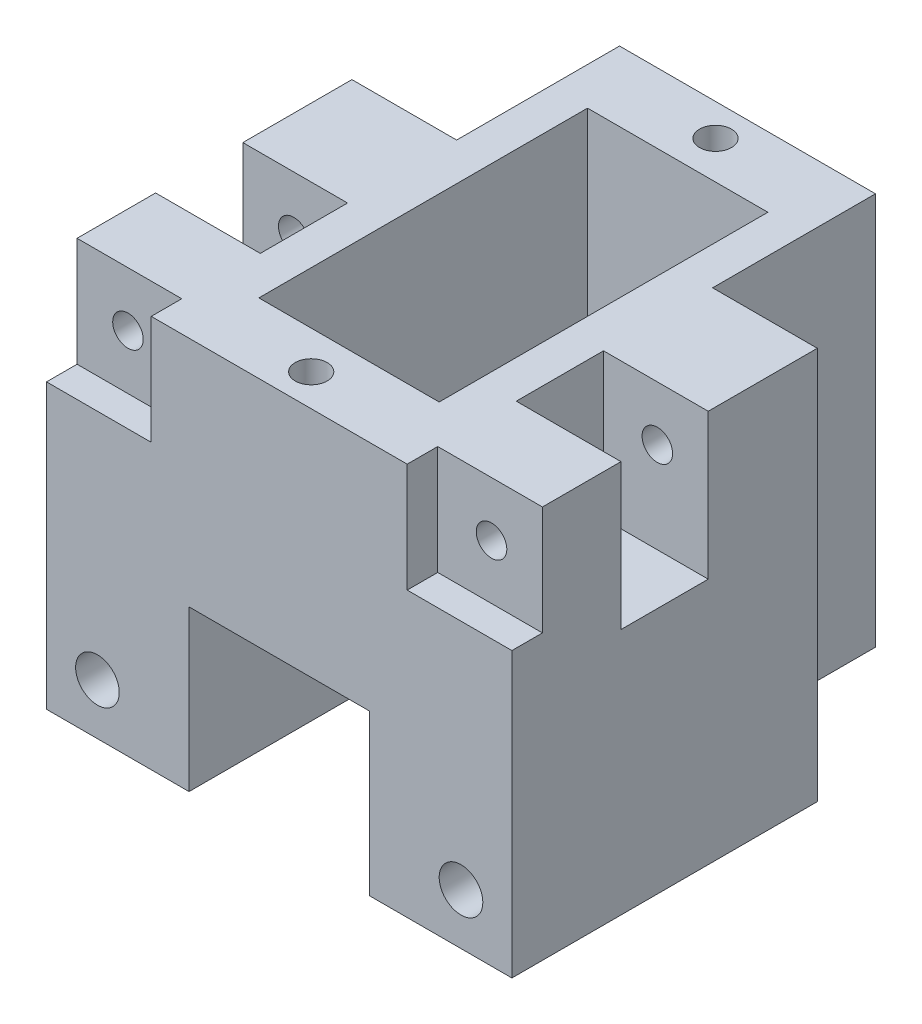
SolidWorks part; units mm, degrees
ref_plane "Front Plane" through (0, 0, 0) normal (0, 0, 1) x (1, 0, 0)
ref_plane "Top Plane" through (0, 0, 0) normal (0, 1, 0) x (1, 0, 0)
ref_plane "Right Plane" through (0, 0, 0) normal (1, 0, 0) x (0, 0, -1)
sketch "Sketch1" plane through (0, 0, 0) normal (0, 1, 0) x (1, 0, 0)
  line L0 (0, 0) -> (200, 0)
  line L1 (200, 0) -> (200, 47.5)
  line L2 (200, 47.5) -> (145, 47.5)
  line L3 (145, 47.5) -> (145, 117.5)
  line L4 (145, 117.5) -> (200, 117.5)
  line L5 (200, 117.5) -> (200, 144.5)
  line L7 (0, 144.5) -> (0, 117.5)
  line L8 (0, 117.5) -> (55, 117.5)
  line L9 (55, 117.5) -> (55, 47.5)
  line L10 (55, 47.5) -> (0, 47.5)
  line L11 (0, 47.5) -> (0, 0)
  line L12 (100, 0) -> (100, 178.8662) construction
  line L13 (84, 77) -> (116, 77)
  line L14 (84, 77) -> (84, 98)
  line L15 (84, 98) -> (91.2, 98)
  line L16 (116, 98) -> (116, 77)
  line L17 (93.8, 98) -> (93.8, 77)
  line L18 (106.2, 98) -> (106.2, 77)
  line L19 (93.8, 81.8) -> (106.2, 81.8)
  line L20 (93.8, 98) -> (93.8, 104.4)
  line L21 (93.8, 104.4) -> (106.2, 104.4)
  line L22 (106.2, 104.4) -> (106.2, 98)
  line L23 (108.8, 98) -> (116, 98)
  line L24 (91.2, 98) -> (91.2, 109.2)
  line L25 (91.2, 109.2) -> (108.8, 109.2)
  line L26 (108.8, 109.2) -> (108.8, 98)
  line L27 (80, 0) -> (80, -20)
  line L28 (80, -20) -> (90, -20)
  line L29 (90, -20) -> (90, 0)
  line L30 (120, -20) -> (110, -20)
  line L31 (110, -20) -> (110, 0)
  line L32 (120, 0) -> (120, -20)
  line L33 (20, 144.5) -> (180, 144.5) construction
  line L34 (145, 117.5) -> (200, 144.5)
  line L35 (0, 144.5) -> (55, 117.5)
  arc A0 (0, 144.5) -> (200, 144.5) centre (100, 16.1913) cw
  arc A1 (20, 144.5) -> (180, 144.5) centre (100, 29.6087) cw construction
  circle A2 centre (91, 93) radius 1.5
  circle A3 centre (91, 82) radius 1.5
  circle A4 centre (109, 82) radius 1.5
  circle A5 centre (109, 93) radius 1.5
  point P12 (100, 0)
  point P14 (100, 77)
  point P21 (100, 85.5)
  point P34 (80, 0)
  point P43 (55, 82.5)
  point P48 (100, 144.5)
  dimension "D23" = 162.6749
  dimension "D26" = 140
  dimension "D28" = 3
  dimension "D29" = 3
  dimension "D30" = 3
  dimension "D31" = 3
  dimension "D32" = 5
  dimension "D33" = 5
  dimension "D3" = 35
  dimension "D4" = 200
  dimension "D5" = 45
  dimension "D6" = 45
  dimension "D7" = 77
  dimension "D8" = 32
  dimension "D9" = 21
  dimension "D10" = 16
  dimension "D11" = 12.4
  dimension "D12" = 6.2
  dimension "D13" = 4.8
  dimension "D14" = 22.6
  dimension "D15" = 4.8
  dimension "D16" = 7.2
  dimension "D17" = 7.2
  dimension "D18" = 20
  dimension "D19" = 10
  dimension "D20" = 20
  dimension "D21" = 5.5
  dimension "D22" = 70
  dimension "D24" = 27
  dimension "D25" = 27
  dimension "D27" = 160
  dimension "D34" = 7
  dimension "D36" = 7
extrude "Boss-Extrude2" add sketch "Sketch1" along normal blind 27 from offset 2 contours L26 L25 L24 L15 L14 L13 L17 L20 L21 L22 L18 L16 L23 | L19 L17 L13 L18 | A3 | A2 | A5 | A4 region at (84.454, 0, -87.5) region at (100, 0, -79.4) region at (91, 0, -93) region at (91, 0, -82) region at (109, 0, -82) region at (109, 0, -93)
ref_plane "Plane1" through (0, 29, 0) normal (0, 1, 0) x (1, 0, 0)
sketch "Sketch2" plane through (0, 29, 0) normal (0, 1, 0) x (1, 0, 0)
  line L0 (84, 78.9953) -> (84, 84.5)
  line L1 (84, 84.5) -> (84, 77)
  line L2 (116, 80.7116) -> (116, 85.2116)
  line L3 (116, 85.2116) -> (116, 77)
  line L4 (116, 79.1) -> (108.8, 79.1)
  line L5 (108.8, 79.1) -> (108.8, 77)
  line L6 (91.2, 77) -> (91.2, 79.1)
  line L7 (91.2, 79.1) -> (84, 79.1)
  line L8 (91.2, 98) -> (84, 98)
  line L11 (91.2, 98) -> (84, 98)
  line L13 (84, 98) -> (84, 77)
  line L24 (116, 84.5) -> (108.8, 84.5)
  line L25 (108.8, 84.5) -> (108.8, 90.5)
  line L26 (108.8, 90.5) -> (116, 90.5)
  line L27 (100, 0) -> (100, 178.8662) construction
  line L28 (100, 0) -> (100, 178.8662) construction
  line L29 (84, 84.5) -> (91.2, 84.5)
  line L30 (91.2, 84.5) -> (91.2, 90.5)
  line L31 (91.2, 90.5) -> (84, 90.5)
  line L32 (84, 98) -> (84, 77)
  line L44 (84, 77) -> (116, 77)
  line L45 (84, 77) -> (116, 77)
  line L47 (116, 77) -> (116, 98)
  line L49 (116, 77) -> (116, 98)
  line L51 (116, 98) -> (108.8, 98)
  line L53 (116, 98) -> (108.8, 98)
  line L55 (108.8, 98) -> (108.8, 109.2)
  line L56 (108.8, 98) -> (108.8, 109.2)
  line L57 (108.8, 109.2) -> (91.2, 109.2)
  line L58 (108.8, 109.2) -> (91.2, 109.2)
  line L59 (91.2, 109.2) -> (91.2, 98)
  line L60 (91.2, 109.2) -> (91.2, 98)
  point P21 (116, 87.5)
  dimension "D4" = 7.2
  dimension "D5" = 7.2
  dimension "D6" = 6
  dimension "D7" = 3
  dimension "D1" = 0
extrude "Cut-Extrude1" cut sketch "Sketch2" against normal blind 7.5 contours L5 L45 L3 L4 | L1 L45 L6 L7 L0 region at (87.6, 29, -78.05) region at (112.4, 29, -78.05)
ref_plane "Plane2" through (0, 0, -77) normal (0, 0, 1) x (1, 0, 0)
sketch "Sketch3" plane through (0, 0, -77) normal (0, 0, 1) x (1, 0, 0)
  line L0 (93.8, 29) -> (106.2, 29) construction
  line L1 (93.8, 29) -> (106.2, 29)
  line L2 (93.8, 29) -> (93.8, 2) construction
  line L4 (106.2, 29) -> (106.2, 2) construction
  line L5 (93.8, 13) -> (106.2, 13)
  line L6 (93.8, 13) -> (93.8, 2)
  line L7 (106.2, 13) -> (106.2, 2)
  line L8 (84, 2) -> (116, 2) construction
  line L9 (93.8, 29) -> (93.8, 2) construction
  line L10 (106.2, 29) -> (106.2, 2) construction
  line L11 (84, 2) -> (116, 2)
  dimension "D1" = 16
extrude "Cut-Extrude2" cut sketch "Sketch3" against normal through all both and the other way through all contours L6 L7 L5 region at (100, 7.5, -77)
extrude "Cut-Extrude3" cut sketch "Sketch2<3>" against normal blind 10 contours L26 L25 L24 L49 | L30 L31 L32 L29 region at (87.6, 29, -87.5) region at (112.4, 29, -87.5)
sketch "Sketch2<3>" plane through (0, 29, 0) normal (0, 1, 0) x (1, 0, 0) same geometry as "Sketch2"
sketch "Sketch7" plane through (0, 0, -77) normal (0, 0, 1) x (1, 0, 0)
  line L0 (116, 29) -> (108.8, 29) construction
  line L1 (108.8, 29) -> (108.8, 21.5) construction
  line L2 (108.8, 21.5) -> (116, 21.5) construction
  line L3 (116, 21.5) -> (116, 29) construction
  line L4 (91.2, 29) -> (84, 29) construction
  line L5 (84, 29) -> (84, 21.5) construction
  line L6 (84, 21.5) -> (91.2, 21.5) construction
  line L7 (91.2, 21.5) -> (91.2, 29) construction
  line L8 (116, 29) -> (108.8, 29) construction
  line L9 (108.8, 29) -> (108.8, 21.5) construction
  line L10 (108.8, 21.5) -> (116, 21.5) construction
  line L11 (116, 21.5) -> (116, 29) construction
  line L12 (91.2, 29) -> (84, 29) construction
  line L13 (84, 29) -> (84, 21.5)
  line L14 (84, 21.5) -> (91.2, 21.5) construction
  line L15 (91.2, 21.5) -> (91.2, 29) construction
  line L16 (106.2, 2) -> (116, 2) construction
  line L21 (84, 21.5) -> (84, 2) construction
  line L22 (116, 21.5) -> (116, 2) construction
  line L24 (84, 2) -> (93.8, 2) construction
  line L25 (84, 21.5) -> (84, 2) construction
  line L26 (116, 21.5) -> (116, 2) construction
  line L27 (106.2, 2) -> (116, 2) construction
  line L28 (91, 2) -> (91, 9) construction
  line L29 (91, 9) -> (84, 9) construction
  line L30 (109, 9) -> (109, 2) construction
  line L31 (109, 9) -> (116, 9) construction
  line L32 (84, 9) -> (91, 2) construction
  line L33 (91, 9) -> (84, 2) construction
  line L34 (109, 9) -> (116, 2) construction
  line L35 (109, 2) -> (116, 9) construction
  circle A0 centre (112.5, 25.25) radius 1.05
  circle A1 centre (87.5, 25.25) radius 1.05
  circle A2 centre (87.5, 5.5) radius 1.5
  circle A3 centre (112.5, 5.5) radius 1.5
  dimension "D1" = 2.1
  dimension "D2" = 2.1
  dimension "D7" = 3
  dimension "D8" = 3
  dimension "D3" = 7
  dimension "D4" = 7
  dimension "D5" = 7
  dimension "D6" = 7
  dimension "D9" = 3.75
extrude "Cut-Extrude9" cut sketch "Sketch7" against normal through all contours A1 | A0 | A2 | A3 region at (87.5, 25.25, -77)
extrude "Cut-Extrude12" cut sketch "Sketch1<8>" along normal blind 12 contours A4 | A5 | A3 | A2 region at (91, 0, -93) region at (91, 0, -82) region at (109, 0, -82) region at (109, 0, -93)
sketch "Sketch1<8>" plane through (0, 0, 0) normal (0, 1, 0) x (1, 0, 0) same geometry as "Sketch1"
ref_plane "Plane3" through (0, 29, 0) normal (0, 1, 0) x (1, 0, 0)
sketch "Sketch8" plane through (0, 29, 0) normal (0, 1, 0) x (1, 0, 0)
  line L0 (100, 0) -> (100, 178.8662) construction
  line L2 (100, 107) -> (100, 79.2) construction
  line L3 (100, 79.2) -> (100, 107) construction
  line L6 (100, 79.2) -> (100, 77) construction
  line L7 (100, 107) -> (100, 109.2) construction
  line L8 (91.2, 109.2) -> (108.8, 109.2) construction
  point P0 (100, 107)
  point P1 (100, 79.2)
  point P8 (100, 93.1)
  dimension "D1" = 27.8
hole_wizard "Ø2.2 (2.2) Diameter Hole1" positions "Sketch9" profile "Sketch10" hole size "Ø2.2" standard "ISO" end condition up to next
sketch "Sketch9" plane through (0, 29, 0) normal (0, 1, 0) x (1, 0, 0)
  point P0 (100, 79.2)
  point P3 (100, 107)
sketch "Sketch10" plane through (100, 29, -79.2) normal (1, 0, 0) x (0, 0, 1)
  line L0 (0, 0) -> (0, 16)
  line L1 (0, 16) -> (1.1, 16)
  line L2 (1.1, 16) -> (1.1, 0)
  line L5 (1.1, 0) -> (0, 0)
  line L11 (0, -6.35) -> (0, 107.95) construction
  dimension "Thru Hole Dia." = 2.2
  dimension "Thru Hole Depth" = 16
equation "\"w9\"=2"
